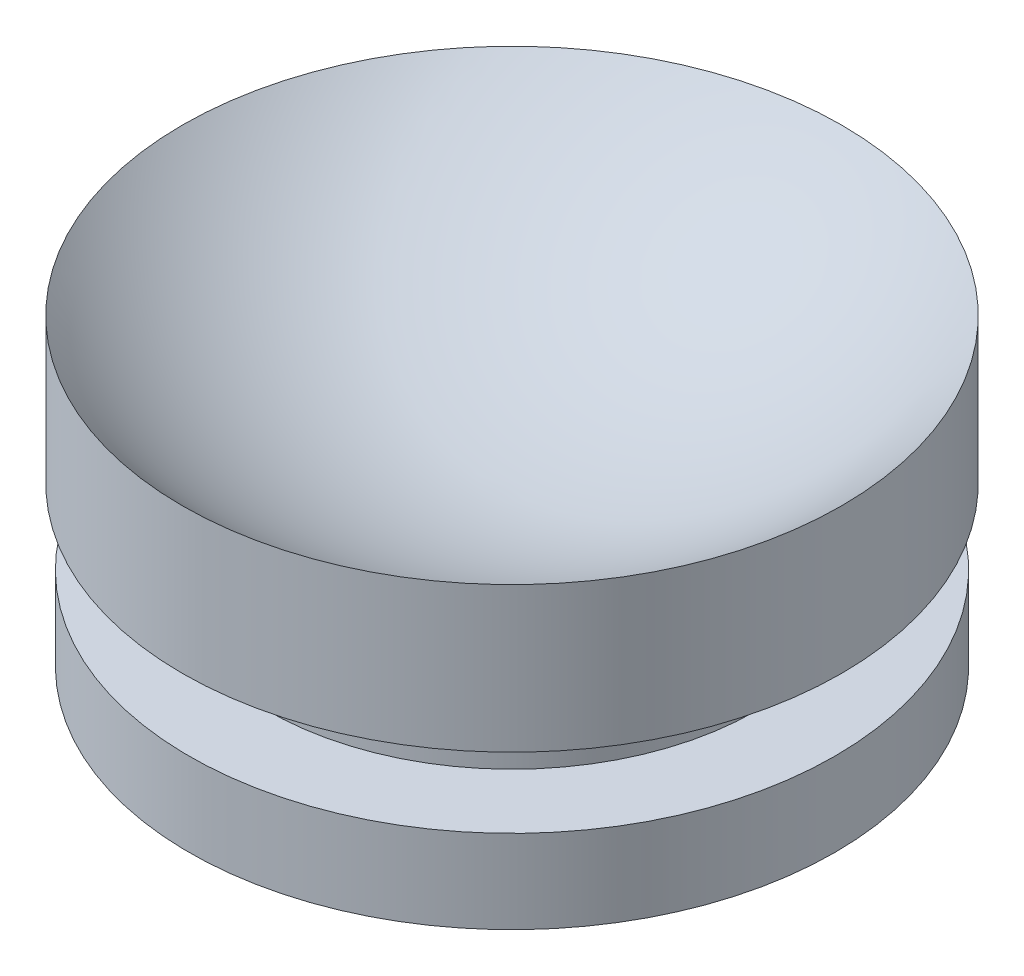
SolidWorks part; units mm, degrees
ref_plane "Front Plane" through (0, 0, 0) normal (0, 0, 1) x (1, 0, 0)
ref_plane "Top Plane" through (0, 0, 0) normal (0, 1, 0) x (1, 0, 0)
ref_plane "Right Plane" through (0, 0, 0) normal (1, 0, 0) x (0, 0, -1)
sketch "Sketch3" plane through (0, 0, 0) normal (0, 0, 1) x (1, 0, 0)
  line L0 (0, 0) -> (9.8315, 0)
  line L1 (9.8315, 0) -> (9.8315, 2.54)
  line L2 (9.8315, 2.54) -> (7.4404, 2.54)
  line L3 (7.4404, 2.54) -> (7.4404, 4.826)
  line L4 (7.4404, 4.826) -> (10.0385, 4.826)
  line L5 (10.0385, 4.826) -> (10.0385, 9.2456)
  line L6 (0, 0) -> (0, 4.826)
  line L8 (7.4404, 4.826) -> (0, 4.826)
  arc A0 (0, 4.826) -> (10.0385, 9.2456) centre (0, 18.4364) ccw
  dimension "D1" = 2.54
  dimension "D2" = 2.286
  dimension "D3" = 4.4196
revolve "Revolve3" add sketch "Sketch3" angle 360 about L6 region at (4.4314, 2.2476, 0) region at (7.6177, 6.1046, 0)
ref_axis "Axis1" through (0, -0.4623, 0) along (0, 1, 0)
